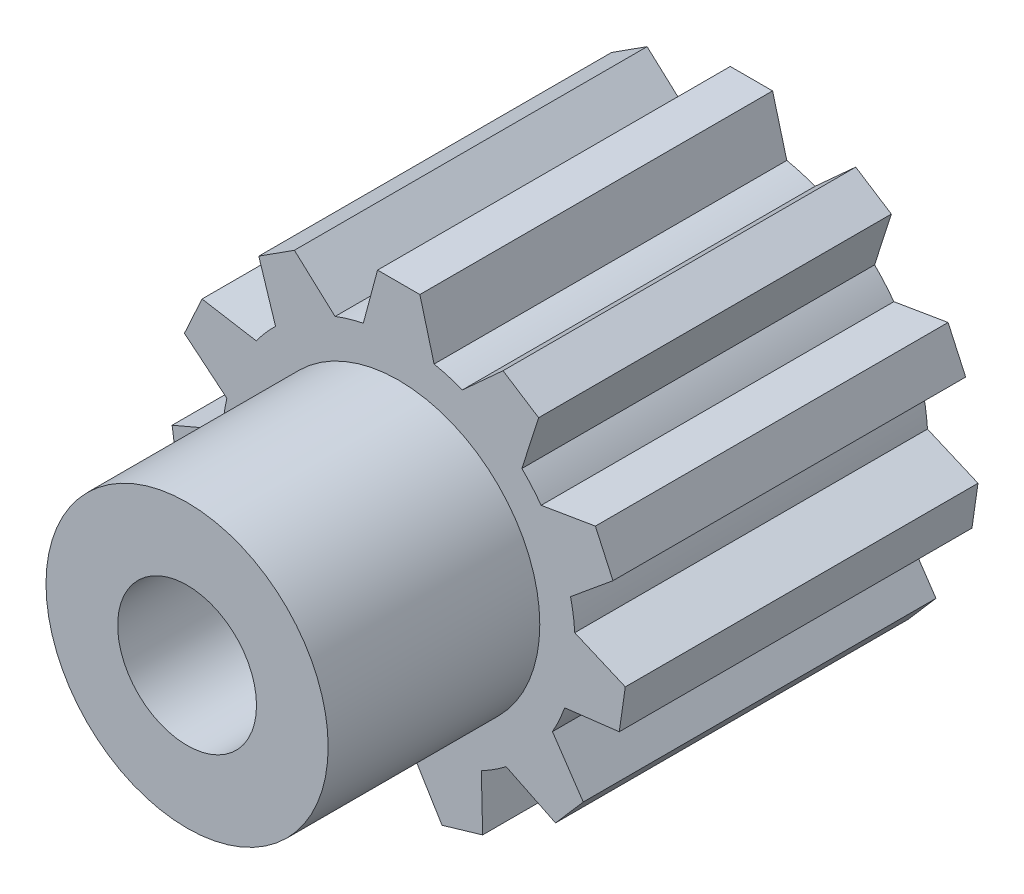
SolidWorks part; units mm, degrees
ref_plane "Front Plane" through (0, 0, 0) normal (0, 0, 1) x (1, 0, 0)
ref_plane "Top Plane" through (0, 0, 0) normal (0, 1, 0) x (1, 0, 0)
ref_plane "Right Plane" through (0, 0, 0) normal (1, 0, 0) x (0, 0, -1)
sketch "Sketch1" plane through (0, 0, 0) normal (0, 0, 1) x (1, 0, 0)
  circle A0 centre (0, 0) radius 6.35
  dimension "D1" = 12.7
extrude "Boss-Extrude1" add sketch "Sketch1" along normal blind 12.7
sketch "Sketch2" plane through (0, 0, 12.7) normal (0, 0, 1) x (1, 0, 0)
  line L0 (0, 0) -> (0, 8.1332) construction
  line L1 (0, 8.1332) -> (-0.762, 8.1332)
  line L2 (-0.762, 8.1332) -> (-1.3884, 5.7953)
  line L3 (0, 8.1332) -> (0.762, 8.1332)
  line L4 (0.762, 8.1332) -> (1.3884, 5.7953)
  line L5 (1.3884, 5.7953) -> (-1.3884, 5.7953)
  dimension "D1" = 75
  dimension "D2" = 75
  dimension "D3" = 0.762
  dimension "D4" = 0.762
  dimension "D5" = 5.7953
  dimension "D6" = 8.1332
extrude "Boss-Extrude2" add sketch "Sketch2" against normal blind 12.7
pattern_circular "CirPattern1" count 11 over 360 about axis through (0, 0, 12.7) along (0, 0, -1) of "Boss-Extrude2"
sketch "Sketch3" plane through (0, 0, 12.7) normal (0, 0, 1) x (1, 0, 0)
  circle A0 centre (0, 0) radius 5.08
  dimension "D1" = 10.16
extrude "Boss-Extrude3" add sketch "Sketch3" along normal blind 7.62 contours A0
sketch "Sketch4" plane through (0, 0, 20.32) normal (0, 0, 1) x (1, 0, 0)
  circle A0 centre (0, 0) radius 2.5
  dimension "D1" = 5
extrude "Cut-Extrude1" cut sketch "Sketch4" against normal through all
